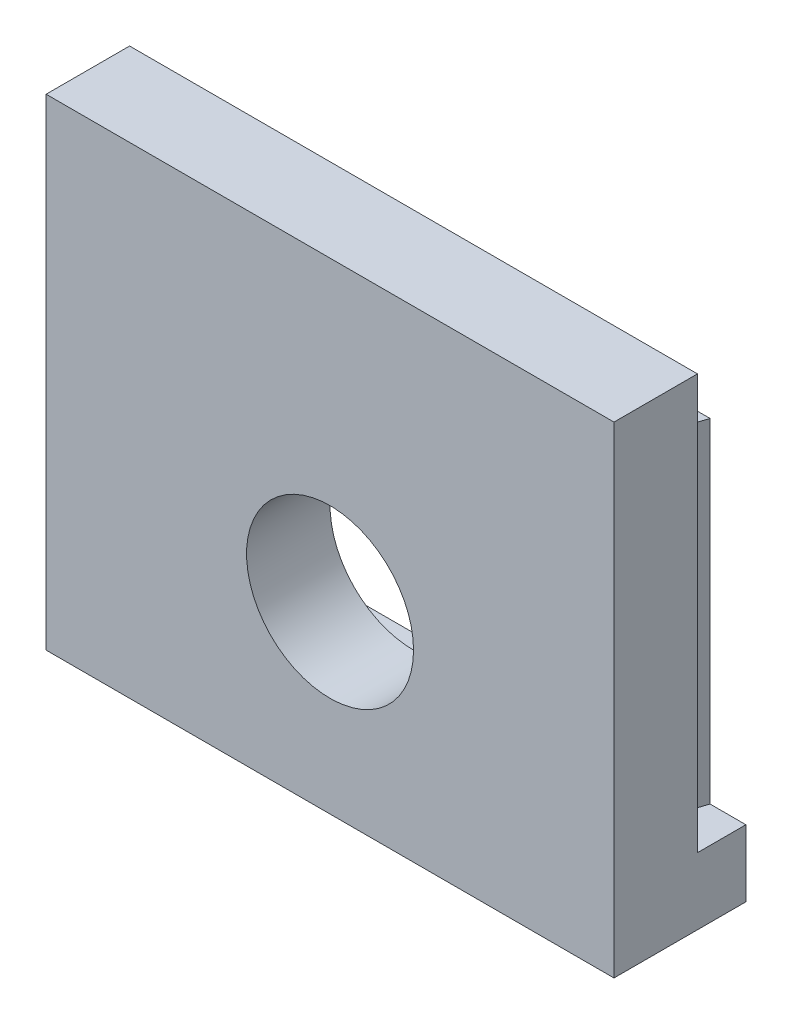
SolidWorks part; units mm, degrees
ref_plane "前视基准面" through (0, 0, 0) normal (0, 0, 1) x (1, 0, 0)
ref_plane "上视基准面" through (0, 0, 0) normal (0, 1, 0) x (1, 0, 0)
ref_plane "右视基准面" through (0, 0, 0) normal (1, 0, 0) x (0, 0, -1)
sketch "草图1" plane through (0, 0, 0) normal (0, 0, 1) x (1, 0, 0)
  line L0 (0, 89.8936) -> (0, -98.0496) construction
  line L1 (-116.3121, 0) -> (122.695, 0) construction
  line L2 (-20, 26) -> (20, 26)
  line L3 (20, 26) -> (30, 0)
  line L4 (-20, 26) -> (-30, 0)
  line L5 (20, -26) -> (30, 0)
  line L6 (-20, -26) -> (20, -26)
  line L7 (-20, -26) -> (-30, 0)
  line L8 (-64.4686, -4) -> (71.1496, -4) construction
  circle A0 centre (0, -15) radius 5
  point P10 (0, 26)
  dimension "D5" = 10
  dimension "D1" = 52
  dimension "D2" = 40
  dimension "D3" = 60
  dimension "D4" = 11
  dimension "D6" = 30
extrude "凸台-拉伸1" add sketch "草图1" against normal blind 5
ref_plane "基准面2" through (0, 8.6651, -15.0083) normal (0, 0.5, -0.866) x (-1, 0, 0)
ref_plane "基准面3" through (0, 24.6651, -42.7211) normal (0, 0.5, -0.866) x (-1, 0, 0)
sketch "草图2" plane through (0, 0, -5) normal (0, 0, -1) x (-1, 0, 0)
  line L0 (-20, 26) -> (20, 26) construction
  line L1 (-20, 26) -> (20, 26)
  line L2 (-21.9231, 21) -> (21.9231, 21)
  line L3 (-30, 0) -> (-20, 26) construction
  line L4 (20, 26) -> (30, 0) construction
  line L5 (21.9231, 21) -> (20, 26)
  line L6 (-20, 26) -> (-21.9231, 21)
  dimension "D1" = 5
extrude "凸台-拉伸2" add sketch "草图2" along normal up to surface (36.9504 mm away) up to plane "基准面3"
sketch "草图3" plane through (0, 0, -5) normal (0, 0, -1) x (-1, 0, 0)
  line L0 (30, 0) -> (20, -26) construction
  line L1 (20, -26) -> (-20, -26) construction
  line L2 (-20, -26) -> (-30, 0) construction
  line L3 (23.8462, -16) -> (20, -26)
  line L4 (20, -26) -> (-20, -26)
  line L5 (-20, -26) -> (-23.8462, -16)
  line L6 (-23.8462, -16) -> (-19.5605, -16)
  line L7 (-19.5605, -16) -> (-17.2528, -22)
  line L8 (-17.2528, -22) -> (17.2528, -22)
  line L9 (0, -4.2824) -> (0, -32.9608) construction
  line L10 (19.5605, -16) -> (17.2528, -22)
  line L11 (23.8462, -16) -> (19.5605, -16)
  dimension "D1" = 10
  dimension "D2" = 4
  dimension "D3" = 4
extrude "凸台-拉伸3" add sketch "草图3" along normal blind 55
ref_plane "基准面1" through (0, -2, 0) normal (0, 1, 0) x (1, 0, 0)
sketch "草图4" plane through (0, -2, 0) normal (0, 1, 0) x (1, 0, 0)
  line L0 (0, 48.4151) -> (0, -2.696) construction
  line L1 (12.5, 9.9075) -> (12.5, -2.1087) construction
  line L2 (11, 5) -> (10, 8) construction
  line L5 (-5, 0) -> (5, 0) construction
  line L6 (14, 5) -> (11, 5) construction
  line L7 (14, 5) -> (15, 8) construction
  line L8 (15, 8) -> (10, 8) construction
  line L11 (11.1054, 5) -> (10.1387, 7.9)
  line L12 (14.8613, 7.9) -> (10.1387, 7.9)
  line L13 (13.8946, 5) -> (14.8613, 7.9)
  line L15 (13.9279, 5.1) -> (11.0721, 5.1) construction
  line L16 (11.0721, 5.1) -> (10.1387, 7.9) construction
  line L17 (13.9279, 5.1) -> (14.8613, 7.9) construction
  line L18 (11.1054, 5) -> (13.8946, 5)
  line L19 (-11.1054, 5) -> (-13.8946, 5)
  line L20 (-13.8946, 5) -> (-14.8613, 7.9)
  line L21 (-14.8613, 7.9) -> (-10.1387, 7.9)
  line L22 (-11.1054, 5) -> (-10.1387, 7.9)
  point P6 (12.5, 5)
  point P8 (12.5, 8)
  dimension "D1" = 12.5
  dimension "D2" = 5
  dimension "D3" = 3
  dimension "D4" = 3
  dimension "D5" = 5
  dimension "D6" = 0.1
extrude "凸台-拉伸4" add sketch "草图4" against normal up to surface (20 mm away) up to face at (0, -22, -32.5)
fillet "圆角1" radius 10 5 edges at (-21.7033, -16, -60) (21.7033, -16, -5) (-21.7033, -16, -5) (-20.9615, 23.5, -43.3938) (20.9615, 23.5, -43.3938)
chamfer "倒角1" distance 1 angle 45 5 edges at (20, 26, -16.238) (17.5138, 26, -39.2709) (0, 26, -41.9504) (-17.5138, 26, -39.2709) (-20, 26, -16.238)
sketch "草图5" plane through (0, 26, 0) normal (0, 1, 0) x (1, 0, 0)
  line L0 (0, 65.6454) -> (0, -5.9304) construction
  line L1 (-28.454, 22) -> (45.0517, 22) construction
  line L2 (18.259, 0) -> (-18.259, 0) construction
  line L3 (0, 22) -> (5.5562, 27.5562) construction
  circle A0 centre (14, 36) radius 1.65
  circle A1 centre (14, 8) radius 1.65
  circle A2 centre (-14, 8) radius 1.65
  circle A3 centre (-14, 36) radius 1.65
  circle A4 centre (10, 22) radius 1.65
  circle A5 centre (-10, 22) radius 1.65
  circle A6 centre (0, 12) radius 1.65
  circle A7 centre (0, 32) radius 1.65
  dimension "D2" = 3.3
  dimension "D3" = 28
  dimension "D4" = 28
  dimension "D6" = 3.3
  dimension "D1" = 22
  dimension "D5" = 45
  dimension "D7" = 20
extrude "切除-拉伸1" cut sketch "草图5" against normal up to next
sketch "草图6" plane through (0, 0, -7.9) normal (0, 0, -1) x (-1, 0, 0)
  circle A0 centre (0, -15) radius 54.706
extrude "切除-拉伸2" cut sketch "草图6" along normal through all
sketch "草图7" plane through (0, 0, -7.9) normal (0, 0, -1) x (-1, 0, 0)
  line L1 (-17.005, -28.3417) -> (17.005, -28.3417)
  line L2 (-17.005, -28.3417) -> (-17.005, 2.8342)
  line L3 (-17.005, 2.8342) -> (17.005, 2.8342)
  line L4 (17.005, -28.3417) -> (17.005, 2.8342)
  line L5 (-17.005, -28.3417) -> (17.005, 2.8342) construction
  line L6 (-17.005, 2.8342) -> (17.005, -28.3417) construction
  line L7 (-38.888, -56.8162) -> (38.888, -56.8162)
  line L8 (-38.888, -56.8162) -> (-38.888, 31.3087)
  line L9 (-38.888, 31.3087) -> (38.888, 31.3087)
  line L10 (38.888, -56.8162) -> (38.888, 31.3087)
  line L11 (-38.888, -56.8162) -> (38.888, 31.3087) construction
  line L12 (-38.888, 31.3087) -> (38.888, -56.8162) construction
  point P0 (0, -12.7538)
  point P5 (0, -12.7538)
extrude "切除-拉伸3" cut sketch "草图7" against normal through all
